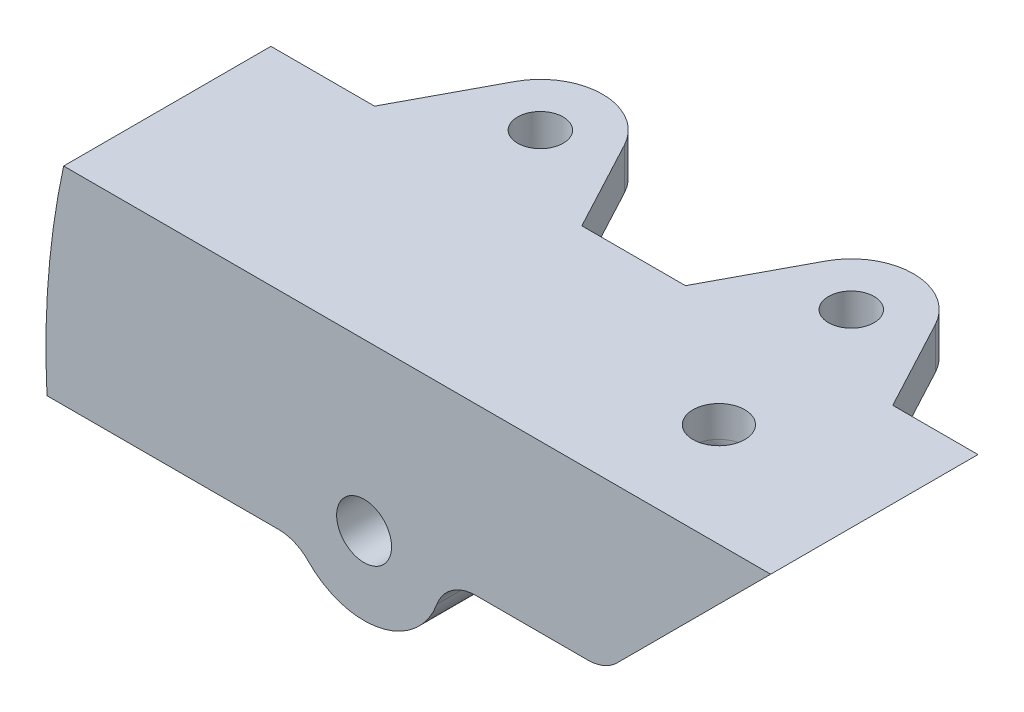
SolidWorks part; units mm, degrees
ref_plane "Front Plane" through (0, 0, 0) normal (0, 0, 1) x (1, 0, 0)
ref_plane "Top Plane" through (0, 0, 0) normal (0, 1, 0) x (1, 0, 0)
ref_plane "Right Plane" through (0, 0, 0) normal (1, 0, 0) x (0, 0, -1)
sketch "Sketch1" plane through (0, 0, 0) normal (0, 0, 1) x (1, 0, 0)
  line L1 (-65, 21) -> (65, 21) construction
  line L2 (-65, 21) -> (-65, 16) construction
  line L3 (-65, 16) -> (65, 16) construction
  line L4 (65, 21) -> (65, 16) construction
  circle A0 centre (0, 0) radius 76.2 construction
  circle A1 centre (0, 0) radius 4 construction
  circle A2 centre (-45, 0) radius 2.5 construction
  circle A3 centre (45, 0) radius 2.5 construction
  dimension "D1" = 152.4
  dimension "D6" = 8
  dimension "D7" = 5
  dimension "D8" = 5
  dimension "D2" = 130
  dimension "D3" = 5
  dimension "D4" = 65
  dimension "D5" = 21
  dimension "D9" = 45
  dimension "D10" = 45
sketch "Sketch2" plane through (0, 0, 0) normal (0, 0, 1) x (1, 0, 0)
  line L0 (-75.5942, -4) -> (-25.764, -4)
  line L1 (-25.764, -4) -> (-5.764, 16)
  line L2 (-65, 16) -> (65, 16) construction
  line L3 (-5.764, 16) -> (-73.9898, 16)
  line L4 (-37.5, 0) -> (-21.764, 0)
  circle A1 centre (-45, 0) radius 2.65
  circle A2 centre (0, 0) radius 75.7
  circle A3 centre (0, 0) radius 75.7
  circle A4 centre (-45, 0) radius 7.5
  dimension "D2" = 5.3
  dimension "D3" = 15
  dimension "D4" = 20
  dimension "D5" = 20
  dimension "D1" = 0.5
extrude "Boss-Extrude1" add sketch "Sketch2" along normal mid plane 20 contours A4 L0 L1 L3 A3 | L0 A4 A1 | L0 A4 region at (-46.0818, 7.785, 0) region at (-47.0293, 7.0237, 0) region at (-45, -5.4324, 0)
sketch "Sketch3" plane through (0, 0, 0) normal (0, 0, 1) x (1, 0, 0)
  line L0 (-75.4576, 8) -> (-50.4576, 8)
  line L1 (-70.4576, 12.2) -> (-76.4576, 15.2)
  line L2 (-50.4576, 8) -> (-76.4576, 8)
  line L3 (-50.4576, 8) -> (-50.4576, 12.2)
  line L4 (-50.4576, 12.2) -> (-76.4576, 12.2)
  line L5 (-76.4576, 8) -> (-76.4576, 12.2)
  line L6 (-76.4576, 15.2) -> (-76.4576, 12.2)
  line L7 (-5.764, 16) -> (-73.9898, 16) construction
  dimension "D1" = 4.2
  dimension "D2" = 25
  dimension "D3" = 3
  dimension "D4" = 1
  dimension "D5" = 5
  dimension "D6" = 8
revolve "Cut-Revolve1" cut sketch "Sketch3" angle 360 about L0 region at (-63.4576, 10.1, 0) region at (-74.4576, 13.2, 0)
sketch "Sketch5" plane through (0, 16, 0) normal (0, 1, 0) x (1, 0, 0)
  line L0 (-65, 0) -> (65, 0) construction
  line L1 (-5.764, -10) -> (-5.764, 10) construction
  circle A0 centre (-20.764, 0) radius 2.5
  dimension "D1" = 5
  dimension "D2" = 15
sketch "Sketch7" plane through (0, 0, 0) normal (0, 0, 1) x (1, 0, 0)
  line L0 (-50.4576, 8) -> (-25.764, 8)
  line L1 (-50.4576, 12.2) -> (-50.4576, 3.8) construction
  line L2 (-20.764, 13) -> (-20.764, 16)
  line L3 (-65, 16) -> (65, 16) construction
  line L4 (-21.764, 0) -> (-5.764, 16) construction
  arc A0 (-25.764, 8) -> (-20.764, 13) centre (-25.764, 13) ccw
  dimension "D2" = 5
  dimension "D1" = 15
sweep "Cut-Sweep2" cut profiles "Sketch5" path "Sketch7"
chamfer "Chamfer1" distance 3 angle 45 1 edges at (-50.4576, 8, 2.5)
fillet "Fillet4" radius 4 3 edges at (-51.3443, -4, 0) (-37.5, 0, 0) (-21.764, 0, 0)
sketch "Sketch9" plane through (0, 16, 0) normal (0, 1, 0) x (1, 0, 0)
  line L0 (-5.764, 10) -> (-73.9898, 10) construction
  line L2 (-63.9898, 10) -> (-59.2839, 18.8235)
  line L3 (-73.9898, -10) -> (-73.9898, 10) construction
  line L4 (-43.9898, 10) -> (-48.6957, 18.8235)
  circle A0 centre (-53.9898, 16) radius 2.2
  circle A2 centre (-53.9898, 16) radius 6
  line M7 (-5.764, 10) -> (-73.9898, 10)
  dimension "D1" = 4.4
  dimension "D5" = 12
  dimension "D3" = 6
  dimension "D7" = 20
  dimension "D8" = 10
  dimension "D9" = 10
extrude "Boss-Extrude2" add sketch "Sketch9" against normal blind 4 contours A2 A0 | A2 L4 M7 | A2 L2 M7 region at (-60.4098, 16, -12.148) region at (-53.9898, 16, -21.8303) region at (-47.5698, 16, -12.148)
pattern_linear "LPattern1" count 2 spacing 30 along (1, 0, 0) of "Boss-Extrude2"
chamfer "Chamfer2" distance 4 angle 45 2 edges at (-53.9898, 12, -10) (-23.9898, 12, -10)
